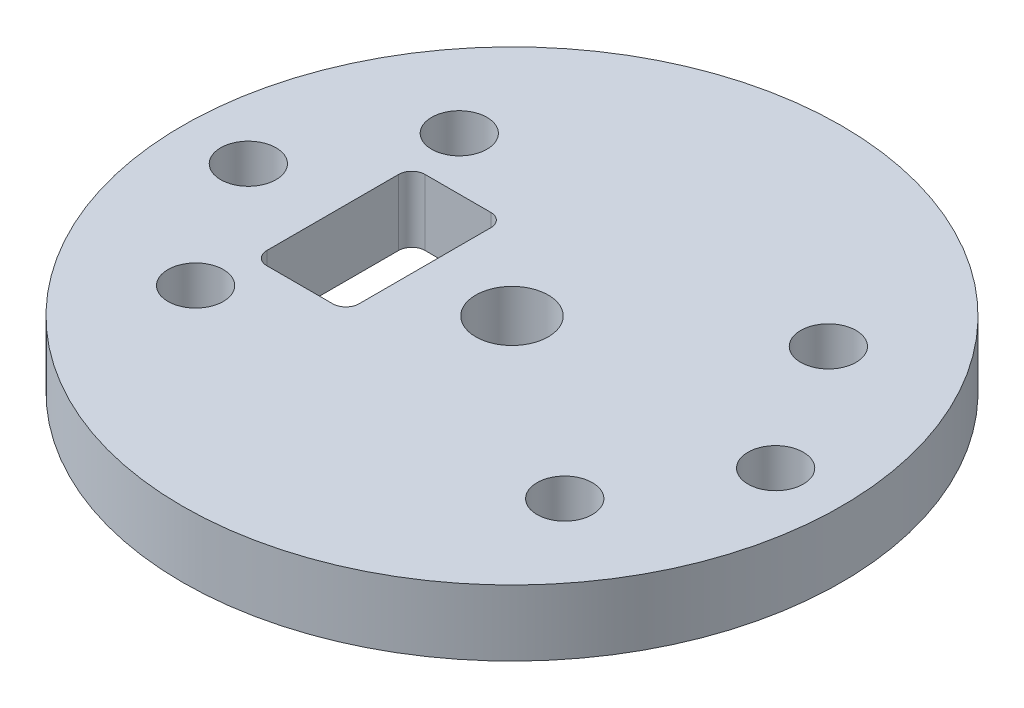
SolidWorks part; units mm, degrees
ref_plane "Front Plane" through (0, 0, 0) normal (0, 0, 1) x (1, 0, 0)
ref_plane "Top Plane" through (0, 0, 0) normal (0, 1, 0) x (1, 0, 0)
ref_plane "Right Plane" through (0, 0, 0) normal (1, 0, 0) x (0, 0, -1)
sketch "Sketch1" plane through (0, 0, 0) normal (0, 1, 0) x (1, 0, 0)
  circle A0 centre (0, 0) radius 31.75
  circle A1 centre (0, 0) radius 3.4925
  dimension "D1" = 63.5
  dimension "D2" = 6.985
extrude "Boss-Extrude1" add sketch "Sketch1" along normal mid plane 6.35
sketch "Sketch2" plane through (0, -3.175, 0) normal (0, -1, 0) x (1, 0, 0)
  circle A0 centre (-17.78, 12.7) radius 2.667 construction
  circle A1 centre (-25.4, 0) radius 2.667 construction
  circle A2 centre (-17.78, -12.7) radius 2.667 construction
  circle A3 centre (17.78, -12.7) radius 2.667 construction
  circle A4 centre (25.4, 0) radius 2.667 construction
  circle A5 centre (17.78, 12.7) radius 2.667 construction
  circle A6 centre (-17.78, 12.7) radius 2.667
  circle A7 centre (-25.4, 0) radius 2.667
  circle A8 centre (-17.78, -12.7) radius 2.667
  circle A9 centre (17.78, -12.7) radius 2.667
  circle A10 centre (25.4, 0) radius 2.667
  circle A11 centre (17.78, 12.7) radius 2.667
  circle A12 centre (-17.78, 12.7) radius 2.2225 construction
  circle A13 centre (-25.4, 0) radius 2.2225 construction
  circle A14 centre (-17.78, -12.7) radius 2.2225 construction
  circle A15 centre (17.78, 12.7) radius 2.2225 construction
  circle A16 centre (25.4, 0) radius 2.2225 construction
  circle A17 centre (17.78, -12.7) radius 2.2225 construction
  dimension "D1" = 4.445
  dimension "D2" = 4.445
  dimension "D3" = 4.445
  dimension "D4" = 4.445
  dimension "D5" = 4.445
  dimension "D6" = 4.445
extrude "Cut-Extrude1" cut sketch "Sketch2" against normal through all
sketch "Sketch4" plane through (0, -3.175, 0) normal (0, -1, 0) x (1, 0, 0)
  line L1 (-8.382, 7.62) -> (-17.272, 7.62)
  line L2 (-8.382, 7.62) -> (-8.382, -7.62)
  line L3 (-8.382, -7.62) -> (-17.272, -7.62)
  line L4 (-9.652, -23.7965) -> (-9.652, 23.7965)
  line L5 (-9.652, 23.7965) -> (-16.002, 6.35)
  line L6 (-16.002, 6.35) -> (-16.002, -6.35)
  line L7 (-16.002, -6.35) -> (-9.652, -23.7965)
  line L8 (-9.652, -23.7965) -> (-9.652, 23.7965)
  line L9 (-9.652, 23.7965) -> (-16.002, 6.35)
  line L10 (-16.002, 6.35) -> (-16.002, -6.35)
  line L11 (-16.002, -6.35) -> (-9.652, -23.7965)
  line L12 (-17.272, 7.62) -> (-17.272, -7.62)
  dimension "D2" = 1.27
  dimension "D3" = 1.27
  dimension "D4" = 1.27
  dimension "D5" = 1.27
  dimension "D1" = 0
extrude "Cut-Extrude4" cut sketch "Sketch4" against normal up to surface (6.35 mm away) contours L8 L3 L2 L1 | L10 L11 L3 L8 L1 L9 | L1 L12 L3 L11 L10 L9 region at (-9.017, -3.175, 0) region at (-12.8086, -3.175, 0) region at (-16.6138, -3.175, 0) up to face at (17.78, 3.175, 10.033)
fillet "Fillet2" radius 1.27 4 edges at (-17.272, 0, -7.62) (-8.382, 0, -7.62) (-8.382, 0, 7.62) (-17.272, 0, 7.62)
